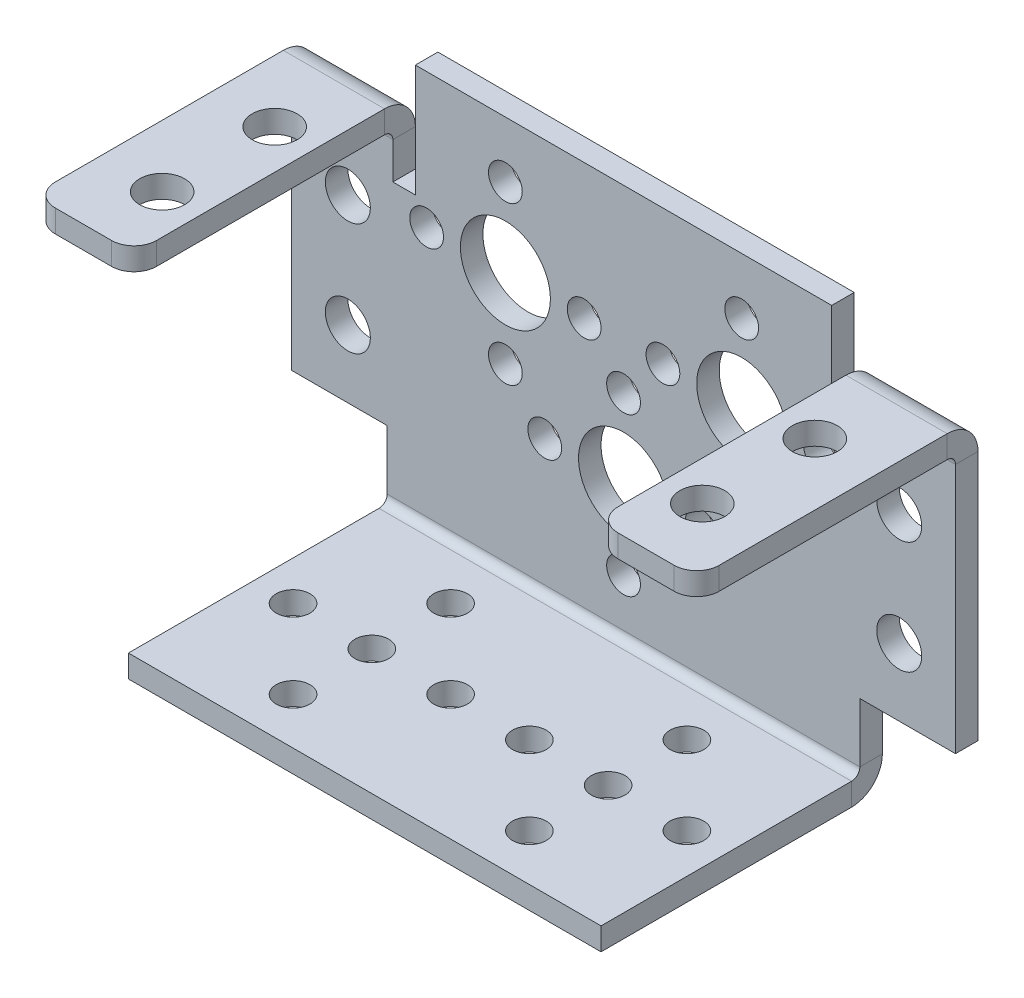
SolidWorks part; units mm, degrees
note: The reader was unsure of these and kept them because the rebuilt part matched: flange length of "边线-法兰1", "边线-法兰2".
material "普通碳钢"
ref_plane "前视" through (0, 0, 0) normal (0, 0, 1) x (1, 0, 0)
ref_plane "上视" through (0, 0, 0) normal (0, 1, 0) x (1, 0, 0)
ref_plane "右视" through (0, 0, 0) normal (1, 0, 0) x (0, 0, -1)
sketch "草图1" plane through (0, 0, 0) normal (0, 0, 1) x (1, 0, 0)
  line L0 (0, 0) -> (9, 0)
  line L1 (9, 0) -> (9, -6)
  line L2 (9, -6) -> (11, -6)
  line L3 (11, -6) -> (11, 4)
  line L4 (11, 4) -> (48, 4)
  line L5 (0, 0) -> (0, -25)
  line L6 (0, -25) -> (8.5, -25)
  line L7 (8.5, -25) -> (8.5, -33)
  line L8 (8.5, -33) -> (50.5, -33)
  line L9 (29.5, 4) -> (29.5, -33) construction
  line L10 (59, 0) -> (59, -25)
  line L11 (48, -6) -> (48, 4)
  line L12 (50, -6) -> (48, -6)
  line L13 (50, 0) -> (50, -6)
  line L14 (59, 0) -> (50, 0)
  line L15 (59, -25) -> (50.5, -25)
  line L16 (50.5, -25) -> (50.5, -33)
  line L17 (15, -8) -> (23, -8) construction
  line L18 (19, -4) -> (19, -12) construction
  line L19 (40, -4) -> (40, -12) construction
  line L20 (36, -8) -> (44, -8) construction
  line L21 (25.5, -19) -> (33.5, -19) construction
  circle A0 centre (19, -8) radius 4
  circle A1 centre (40, -8) radius 4
  circle A2 centre (29.5, -19) radius 4
  circle A3 centre (19, -1) radius 1.5
  circle A4 centre (19, -15) radius 1.5
  circle A5 centre (26, -8) radius 1.5
  circle A6 centre (12, -8) radius 1.5
  circle A7 centre (19, -8) radius 7 construction
  circle A8 centre (33, -8) radius 1.5
  circle A9 centre (40, -15) radius 1.5
  circle A10 centre (47, -8) radius 1.5
  circle A11 centre (40, -1) radius 1.5
  circle A12 centre (29.5, -12) radius 1.5
  circle A13 centre (36.5, -19) radius 1.5
  circle A14 centre (29.5, -26) radius 1.5
  circle A15 centre (22.5, -19) radius 1.5
  circle A16 centre (29.5, -19) radius 7 construction
  circle A17 centre (54, -9) radius 2
  circle A18 centre (54, -19) radius 2
  circle A19 centre (5, -19) radius 2
  circle A20 centre (5, -9) radius 2
  dimension "D9" = 8
  dimension "D11" = 21
  dimension "D12" = 23
  dimension "D13" = 14
  dimension "D14" = 3
  dimension "D15" = 14
  dimension "D16" = 3
  dimension "D17" = 4
  dimension "D18" = 49
  dimension "D19" = 10
  dimension "D20" = 10
  dimension "D21" = 6
  dimension "D1" = 37
  dimension "D2" = 25
  dimension "D3" = 2
  dimension "D4" = 10
  dimension "D5" = 37
  dimension "D6" = 8
  dimension "D7" = 9
  dimension "D8" = 42
  dimension "D10" = 12
base flange "基体-法兰1" sketch "草图1" thickness 2 reverse thickness direction no parameters "D1"=0.7366
edge flange "边线-法兰1" sketch "草图10" flange profiles "草图10", "草图11" flange angle 90 flange length 25 flange position material inside bend radius 0.7366 thickness 2 relief rectangular parameters "D6"=0, "D8"=1
sketch "草图10" plane through (0, 0, 0) normal (0, -1, 0) x (1, 0, 0)
  line L2 (50, 0) -> (50, 23)
  line L3 (50, 23) -> (59, 23)
  line L4 (59, 23) -> (59, 0)
  line L6 (59, 0) -> (50, 0) construction
  line L7 (59, 0) -> (50, 0)
  dimension "D1" = 23
sketch "草图11" plane through (0, 0, 0) normal (0, -1, 0) x (1, 0, 0)
  line L0 (9, 0) -> (0, 0) construction
  line L1 (9, 0) -> (0, 0)
  line L2 (9, 0) -> (9, 23)
  line L3 (9, 23) -> (0, 23)
  line L4 (0, 23) -> (0, 0)
bend "边线折弯1" bend radius 0.7366 bend angle 90 parameters "D5"=1
bend "边线折弯2" bend radius 0.7366 bend angle 90 parameters "D5"=2
edge flange "边线-法兰2" sketch "草图14" flange angle 90 flange length 25 flange position material inside bend radius 0.7366 thickness 2 relief rectangular parameters "D6"=0
sketch "草图14" plane through (0, -33, 0) normal (0, 1, 0) x (-1, 0, 0)
  line L2 (-50.5, 0) -> (-50.5, 23)
  line L3 (-50.5, 23) -> (-8.5, 23)
  line L4 (-8.5, 23) -> (-8.5, 0)
  line L8 (-8.5, 0) -> (-50.5, 0) construction
  line L9 (-8.5, 0) -> (-50.5, 0)
bend "边线折弯3" bend radius 0.7366 bend angle 90 parameters "D5"=3
sketch "草图15" plane through (0, -33, 0) normal (0, -1, 0) x (1, 0, 0)
  line L0 (50.5, 11.8683) -> (8.5, 11.8683) construction
  line L1 (50.5, 23) -> (50.5, 0.7366) construction
  line L2 (8.5, 0.7366) -> (8.5, 23) construction
  line L3 (29.5, 23) -> (29.5, 0.7366) construction
  line L4 (8.5, 23) -> (50.5, 23) construction
  line L5 (8.5, 0.7366) -> (50.5, 0.7366) construction
  circle A0 centre (47, 11.8683) radius 1.5
  circle A1 centre (40, 11.8683) radius 1.5
  circle A2 centre (33, 11.8683) radius 1.5
  circle A3 centre (40, 4.8683) radius 1.5
  circle A4 centre (40, 18.8683) radius 1.5
  circle A5 centre (40, 11.8683) radius 7 construction
  circle A6 centre (12, 11.8683) radius 1.5
  circle A7 centre (19, 18.8683) radius 1.5
  circle A8 centre (26, 11.8683) radius 1.5
  circle A9 centre (19, 11.8683) radius 7 construction
  circle A10 centre (19, 4.8683) radius 1.5
  circle A11 centre (19, 11.8683) radius 1.5
  dimension "D1" = 14
  dimension "D2" = 10.5
  dimension "D3" = 3
  dimension "D4" = 3
extrude "切除-拉伸1" cut sketch "草图15" against normal blind 10 normal cut yes
sketch "草图16" plane through (0, 0, 0) normal (0, 1, 0) x (1, 0, 0)
  line L0 (29.5, -23) -> (29.5, 2) construction
  line L1 (8.5, -23) -> (50.5, -23) construction
  line L2 (48, 2) -> (11, 2) construction
  line L3 (59, -23) -> (50, -23) construction
  circle A0 centre (53.5, -17) radius 2
  circle A1 centre (53.5, -7) radius 2
  circle A2 centre (5.5, -17) radius 2
  circle A3 centre (5.5, -7) radius 2
  dimension "D1" = 4
  dimension "D3" = 6
  dimension "D4" = 48
  dimension "D2" = 10
extrude "切除-拉伸2" cut sketch "草图16" against normal blind 10 normal cut yes
fillet "圆角1" radius 2 4 edges at (59, -1, 23) (50, -1, 23) (9, -1, 23) (0, -1, 23)
sketch "折弯-线1" [suppressed] plane through (0, 0, 0) normal (0, 1, 0) x (1, 0, 0)
sketch "边界框1" [suppressed] plane through (0, 0, 0) normal (0, 1, 0) x (1, 0, 0)
sheet metal parameters "钣金4" thickness 2 parameters "D1"=0.7366
flat pattern "平板型式4" [suppressed]
sketch "折弯-线2" plane through (0, 0, 0) normal (0, 1, 0) x (1, 0, 0)
sketch "边界框2" [suppressed] plane through (0, 0, 0) normal (0, 1, 0) x (1, 0, 0)
sheet metal parameters "钣金5" thickness 2 parameters "D1"=0.7366
flat pattern "平板型式4" [suppressed]
sketch "折弯-线2" plane through (0, 0, 0) normal (0, 1, 0) x (1, 0, 0)
sketch "边界框2" [suppressed] plane through (0, 0, 0) normal (0, 1, 0) x (1, 0, 0)
bend of the flat pattern "展开-<边线折弯1>1"
bend of the flat pattern "展开-<边线折弯2>1"
sheet metal parameters "钣金6" thickness 2 parameters "D1"=0.7366
flat pattern "平板型式4" [suppressed]
sketch "折弯-线2" plane through (0, 0, 0) normal (0, 1, 0) x (1, 0, 0)
sketch "边界框2" [suppressed] plane through (0, 0, 0) normal (0, 1, 0) x (1, 0, 0)
bend of the flat pattern "展开-<边线折弯1>1"
bend of the flat pattern "展开-<边线折弯2>1"
bend of the flat pattern "展开-<边线折弯3>1"
sheet metal parameters "钣金7" thickness 2 parameters "D1"=0.7366
flat pattern "平板型式4"
sketch "折弯-线2" plane through (0, 0, 0) normal (0, 0, 1) x (1, 0, 0)
  line L0 (8.5, -31.6273) -> (50.5, -31.6273) construction
  line L1 (9, -1.3727) -> (0, -1.3727) construction
  line L2 (59, -1.3727) -> (50, -1.3727) construction
  line L3 (8.5, -31.6273) -> (50.5, -31.6273) construction
  line L4 (9, -1.3727) -> (0, -1.3727) construction
  line L5 (59, -1.3727) -> (50, -1.3727) construction
sketch3d "边界框2" [suppressed]
  line L0 (59, 22.2546, 0) -> (59, -55.2546, 0) construction
  line L1 (0, 22.2546, 0) -> (0, -55.2546, 0) construction
  line L2 (59, 22.2546, 0) -> (0, 22.2546, 0) construction
  line L3 (59, -55.2546, 0) -> (0, -55.2546, 0) construction
bend of the flat pattern "展开-<边线折弯1>1"
bend of the flat pattern "展开-<边线折弯2>1"
bend of the flat pattern "展开-<边线折弯3>1"
sheet metal parameters "钣金8" thickness 2 parameters "D1"=0.7366
flat pattern "平板型式4"
sketch "折弯-线2" plane through (0, 0, 0) normal (0, 0, 1) x (1, 0, 0)
  line L0 (8.5, -31.6273) -> (50.5, -31.6273) construction
  line L1 (9, -1.3727) -> (0, -1.3727) construction
  line L2 (59, -1.3727) -> (50, -1.3727) construction
  line L3 (8.5, -31.6273) -> (50.5, -31.6273) construction
  line L4 (9, -1.3727) -> (0, -1.3727) construction
  line L5 (59, -1.3727) -> (50, -1.3727) construction
sketch3d "边界框2" [suppressed]
  line L0 (59, -55.2546, 0) -> (59, 22.2546, 0) construction
  line L1 (0, -55.2546, 0) -> (0, 22.2547, 0) construction
  line L2 (59, -55.2546, 0) -> (0, -55.2546, 0) construction
  line L3 (59, 22.2546, 0) -> (0, 22.2547, 0) construction
bend of the flat pattern "展开-<边线折弯1>1"
bend of the flat pattern "展开-<边线折弯2>1"
bend of the flat pattern "展开-<边线折弯3>1"
